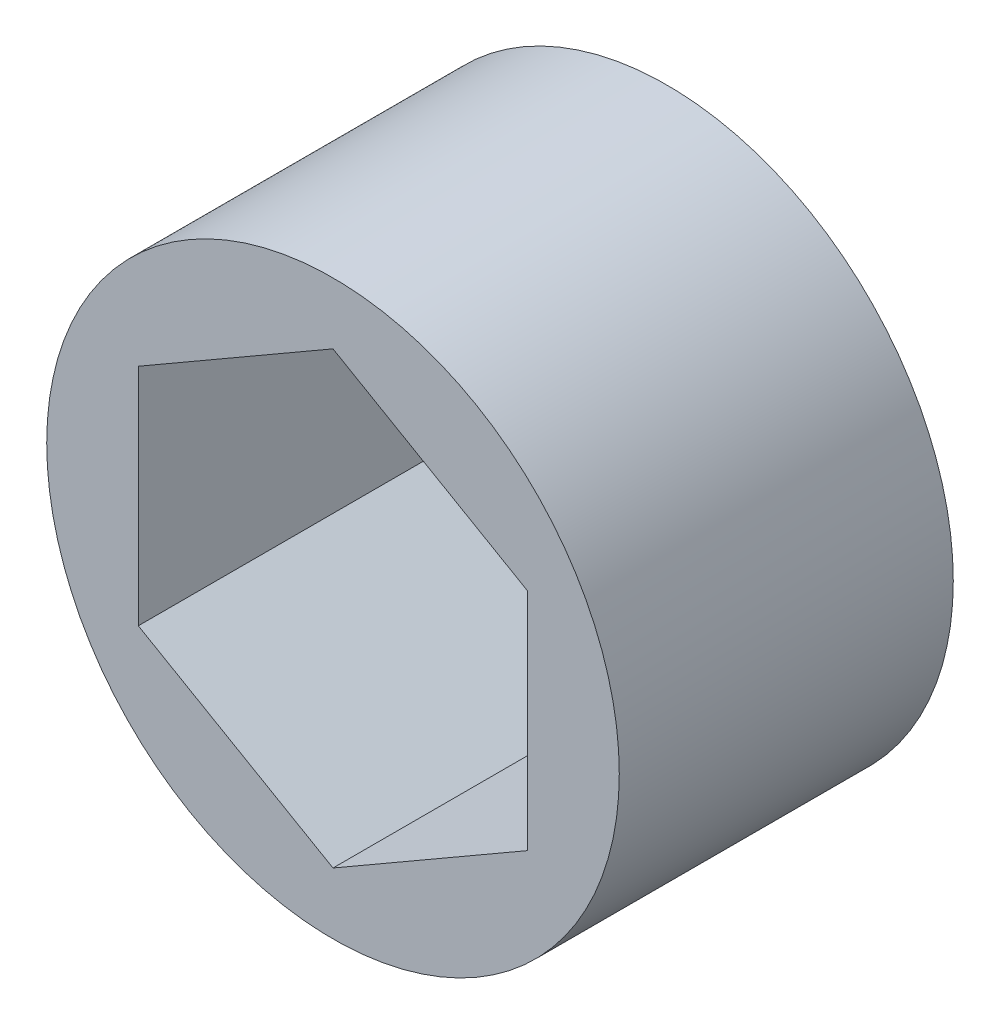
SolidWorks part; units mm, degrees
material "PET"
ref_plane "Front Plane" through (0, 0, 0) normal (0, 0, 1) x (1, 0, 0)
ref_plane "Top Plane" through (0, 0, 0) normal (0, 1, 0) x (1, 0, 0)
ref_plane "Right Plane" through (0, 0, 0) normal (1, 0, 0) x (0, 0, -1)
sketch "Sketch1" plane through (0, 0, 0) normal (0, 0, 1) x (1, 0, 0)
  line L1 (0, 7.479) -> (-6.477, 3.7395)
  line L2 (-6.477, 3.7395) -> (-6.477, -3.7395)
  line L3 (-6.477, -3.7395) -> (0, -7.479)
  line L4 (0, -7.479) -> (6.477, -3.7395)
  line L5 (6.477, -3.7395) -> (6.477, 3.7395)
  line L6 (6.477, 3.7395) -> (0, 7.479)
  circle A0 centre (0, 0) radius 9.525
  circle A1 centre (0, 0) radius 6.477 construction
  dimension "D1" = 12.954
  dimension "D2" = 19.05
extrude "Boss-Extrude1" add sketch "Sketch1" along normal mid plane 11.1125
